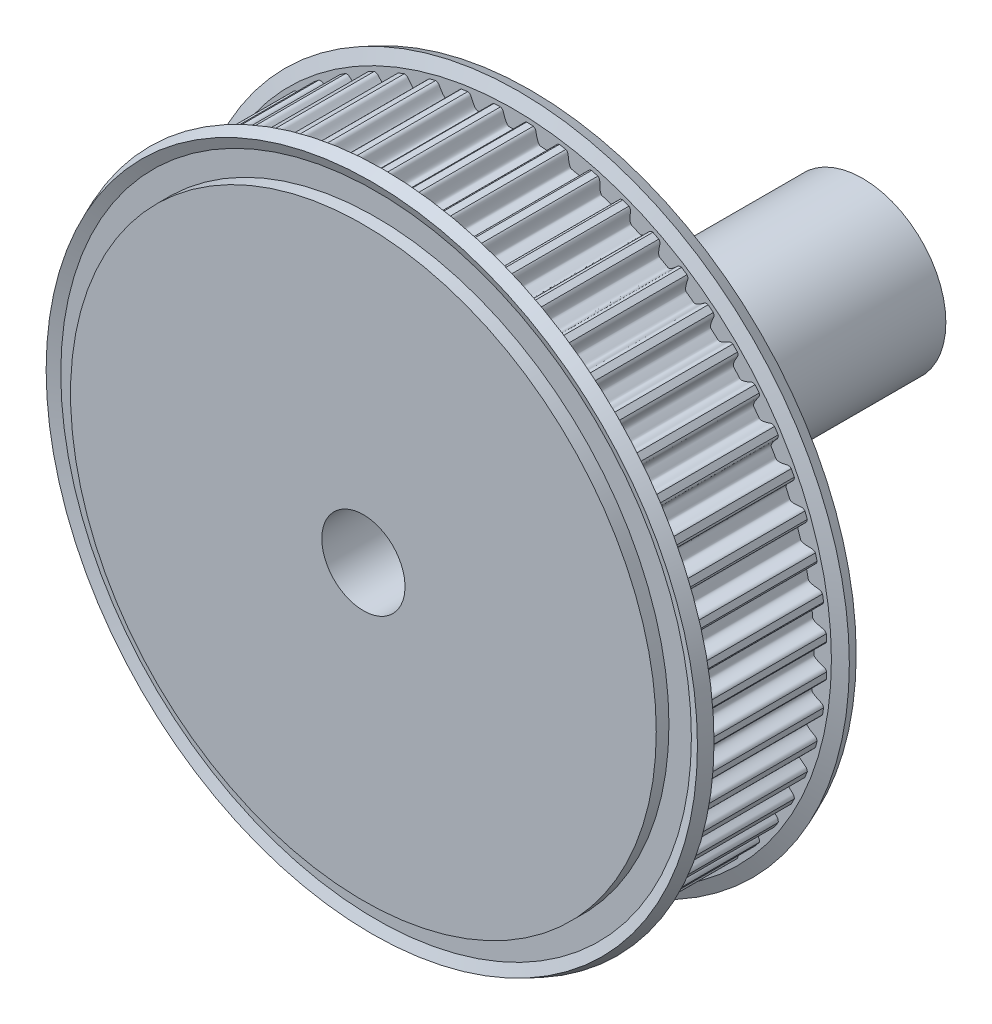
SolidWorks part; units mm, degrees
ref_plane "前视基准面" through (0, 0, 0) normal (0, 0, 1) x (1, 0, 0)
ref_plane "上视基准面" through (0, 0, 0) normal (0, 1, 0) x (1, 0, 0)
ref_plane "右视基准面" through (0, 0, 0) normal (1, 0, 0) x (0, 0, -1)
other "Configuration Table"
ref_axis "基准轴1" through (0, 0, 55) along (0, 0, -1)
sketch "SketchRevolveGearBelt01" plane through (0, 0, 0) normal (1, 0, 0) x (0, 0, -1)
  line L0 (0, 0) -> (1, 0) construction
  line L1 (5.274, 0) -> (5.274, 17.5986)
  line L2 (5.274, 17.5986) -> (4.512, 17.5986)
  line L3 (4.512, 17.5986) -> (4.512, 18.947)
  line L4 (4.512, 18.947) -> (4.7696, 19.569)
  line L5 (4.7696, 19.569) -> (4.0656, 19.8606)
  line L6 (4.0656, 19.8606) -> (3.75, 19.0986)
  line L7 (3.75, 19.0986) -> (3.75, 18.8298)
  line L8 (3.75, 18.8298) -> (-3.75, 18.8298)
  line L9 (-3.75, 18.8298) -> (-3.75, 19.0986)
  line L10 (-3.75, 19.0986) -> (-4.0656, 19.8606)
  line L11 (-4.0656, 19.8606) -> (-4.7696, 19.569)
  line L12 (-4.7696, 19.569) -> (-4.512, 18.947)
  line L13 (-4.512, 18.947) -> (-4.512, 17.5986)
  line L14 (-4.512, 17.5986) -> (-5.274, 17.5986)
  line L15 (-5.274, 17.5986) -> (-5.274, 0)
  line L16 (-5.274, 0) -> (5.274, 0)
  dimension "GearBeltFlange1OutsideLength" = 1.3484
  dimension "GearBeltFlange1X" = 0.2576
  dimension "GearBeltFlange1Y" = 0.622
  dimension "GearBeltFlangeThickness" = 0.762
  dimension "GearBeltFlangeInside" = 0.2688
  dimension "GearBeltOutsideDiameter" = 18.8298
  dimension "GearBeltFlange2X" = 0.2576
revolve "Gates_PowerGrip_GT_2mm, 6mm Belt Width" add sketch "SketchRevolveGearBelt01" angle 360 about L0
sketch "SketchToothGearBelt01" plane through (0, 0, 0) normal (0, 0, 1) x (1, 0, 0)
  arc A0 (18.8246, 0.8608) -> (18.8246, -0.8608) centre (0, 0) cw
  spline S0 degree 3 poles (18.8246, -0.8608) (18.8244, -0.8436) (18.8216, -0.818) (18.813, -0.7848) (18.8042, -0.7607) (18.7932, -0.7375) (18.7799, -0.7155) (18.7646, -0.6948) (18.7474, -0.6758) (18.7284, -0.6584) (18.7079, -0.643) (18.686, -0.6296) (18.6629, -0.6183) (18.6206, -0.6033) (18.5673, -0.5873) (18.5048, -0.5675) (18.4523, -0.5498) (18.4031, -0.5322) (18.357, -0.5145) (18.314, -0.4969) (18.2743, -0.4793) (18.2377, -0.4616) (18.2043, -0.444) (18.174, -0.4264) (18.1469, -0.4087) (18.123, -0.3911) (18.1022, -0.3735) (18.0846, -0.3558) (18.0701, -0.3381) (18.0588, -0.3203) (18.0507, -0.3025) (18.0457, -0.2846) (18.0435, -0.2503) (18.0467, -0.2) (18.0468, -0.1333) (18.0476, -0.0667) (18.0477, 0) (18.0476, 0.0667) (18.0468, 0.1333) (18.0467, 0.2) (18.0435, 0.2503) (18.0457, 0.2846) (18.0507, 0.3025) (18.0588, 0.3203) (18.0701, 0.3381) (18.0846, 0.3558) (18.1022, 0.3735) (18.123, 0.3911) (18.1469, 0.4087) (18.174, 0.4264) (18.2043, 0.444) (18.2377, 0.4616) (18.2743, 0.4793) (18.314, 0.4969) (18.357, 0.5145) (18.4031, 0.5322) (18.4523, 0.5498) (18.5048, 0.5675) (18.5673, 0.5873) (18.6206, 0.6033) (18.6629, 0.6183) (18.686, 0.6296) (18.7079, 0.643) (18.7284, 0.6584) (18.7474, 0.6758) (18.7646, 0.6948) (18.7799, 0.7155) (18.7932, 0.7375) (18.8042, 0.7607) (18.813, 0.7848) (18.8216, 0.818) (18.8244, 0.8436) (18.8246, 0.8608) knots 0 0 0 0 0.019513 0.029269 0.039026 0.048782 0.058538 0.068295 0.078051 0.087808 0.097564 0.10732 0.117077 0.126833 0.158411 0.180602 0.201644 0.221544 0.240311 0.257955 0.274488 0.289925 0.304283 0.317585 0.32986 0.341142 0.351478 0.360929 0.369573 0.377512 0.384878 0.391837 0.398582 0.423956 0.449304 0.474652 0.5 0.525348 0.550696 0.576044 0.601418 0.608163 0.615122 0.622488 0.630427 0.639071 0.648522 0.658858 0.67014 0.682415 0.695717 0.710075 0.725512 0.742045 0.759689 0.778456 0.798356 0.819398 0.841589 0.873167 0.882923 0.89268 0.902436 0.912192 0.921949 0.931705 0.941462 0.951218 0.960974 0.970731 0.980487 1 1 1 1
extrude "ToothExtrudeCutGearBelt01" cut sketch "SketchToothGearBelt01" against normal blind 3.75 and the other way blind 3.75
pattern_circular "Tooth Pattern, 60" count 60 every 6 about axis through (0, 0, 55) along (0, 0, -1) of "ToothExtrudeCutGearBelt01"
sketch "BoreRevolveSketch" plane through (0, 0, 0) normal (1, 0, 0) x (0, 0, -1)
  line L0 (0, 0) -> (1, 0) construction
  line L1 (-5.274, 0) -> (5.274, 0)
  line L2 (5.274, 0) -> (5.274, 5)
  line L3 (5.274, 5) -> (-5.274, 5)
  line L4 (-5.274, 5) -> (-5.274, 0)
  dimension "TaperSide1" = 5
  dimension "TaperSide2" = 5
revolve "BoreRevolveCut" cut sketch "BoreRevolveSketch" angle 360 about L0
sketch "AuxiliarySketchGearBelt01" plane through (0, 0, 0) normal (0, 0, 1) x (1, 0, 0)
  circle A0 centre (0, 0) radius 19.0986 construction
  dimension "PitchDiameter" = 38.1972
sketch "草图5" plane through (0, 0, 5.274) normal (0, 0, 1) x (1, 0, 0)
  circle A1 centre (0, 0) radius 5
extrude "凸台-拉伸1" add sketch "草图5" against normal blind 10
sketch "草图6" plane through (0, 0, -4.726) normal (0, 0, -1) x (-1, 0, 0)
  circle A0 centre (0, 0) radius 2.5
  circle A1 centre (0, 0) radius 5
  dimension "D1" = 5
extrude "凸台-拉伸2" add sketch "草图6" along normal blind 20
sketch "草图7" plane through (0, 0, -4.726) normal (0, 0, -1) x (-1, 0, 0)
  circle A0 centre (0, 0) radius 2.5
extrude "切除-拉伸2" cut sketch "草图7" against normal blind 20
sketch "草图8" plane through (0, 0, 0) normal (0, 1, 0) x (1, 0, 0)
  line L0 (0, 24.726) -> (0, 14.726)
  line L1 (2.5, 24.726) -> (-2.5, 24.726) construction
  line L2 (0, -55) -> (0, 55) construction
  circle A0 centre (0, 14.726) radius 1.5
  dimension "D2" = 3
  dimension "D1" = 10
extrude "切除-拉伸3" cut sketch "草图8" against normal blind 20 contours A0 region at (-1.0307, 0, -13.6953)
ref_plane "基准面1" through (0, 10, 0) normal (0, 1, 0) x (1, 0, 0)
sketch "草图9" plane through (0, 0, 0) normal (1, 0, 0) x (0, 0, -1)
  line L0 (24.726, 0) -> (14.726, 0)
  line L1 (24.726, -5) -> (24.726, 5) construction
  line L2 (-55, 0) -> (55, 0) construction
  circle A0 centre (14.726, 0) radius 1.5
  dimension "D2" = 3
  dimension "D1" = 10
extrude "切除-拉伸4" cut sketch "草图9" against normal blind 20 contours A0 region at (0, 0, -13.2684)
